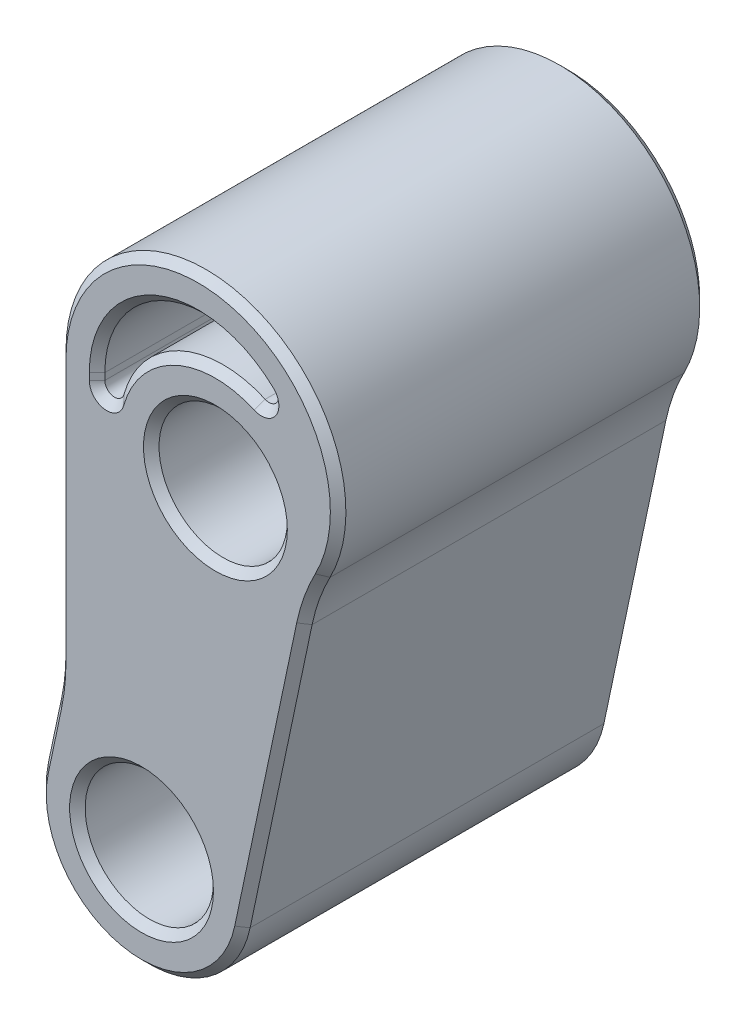
SolidWorks part; units mm, degrees
ref_plane "Front" through (0, 0, 0) normal (0, 0, 1) x (1, 0, 0)
ref_plane "Top" through (0, 0, 0) normal (0, 1, 0) x (1, 0, 0)
ref_plane "Right" through (0, 0, 0) normal (1, 0, 0) x (0, 0, -1)
sketch "Sketch1" plane through (0, 0, 0) normal (0, 0, 1) x (1, 0, 0)
  line L3 (-2.65, 0) -> (-1.65, 0) construction
  line L23 (-0.25, -9) -> (0.75, -9) construction
  line L33 (-2.5929, 0.5474) -> (-4.4929, -8.4526)
  line L34 (0.6929, -9.5474) -> (2.5929, -0.5474)
  circle A0 centre (0, 0) radius 2.65 construction
  circle A3 centre (0, 0) radius 1.65
  circle A12 centre (-1.9, -9) radius 1.65
  circle A13 centre (-1.9, -9) radius 4 construction
  arc A22 (-2.5929, 0.5474) -> (2.5929, -0.5474) centre (0, 0) cw
  arc A28 (-4.4929, -8.4526) -> (0.6929, -9.5474) centre (-1.9, -9) ccw
  dimension "D1" = 3.3
  dimension "D3" = 8
  dimension "D2" = 1
  dimension "D6" = 9
  dimension "D4" = 1.9
extrude "Boss-Extrude1" add sketch "Sketch1" along normal mid plane 9.5 contours A3 region at (-0.95, -4.5, 0)
sketch "Sketch2" plane through (0, 0, 0) normal (0, 0, 1) x (1, 0, 0)
  line L0 (-4.0437, -6.3253) -> (-4.0437, 0.9516)
  line L1 (0, 0) -> (0, 8.0844) construction
  line L2 (0, 0) -> (-0.4437, 0.9516) construction
  line L3 (-0.4437, 0.9516) -> (-1.7961, 3.8518) construction
  line L4 (-1.7961, 3.8518) -> (-1.9652, 4.2143) construction
  line L5 (-2.5929, 0.5474) -> (-4.4929, -8.4526) construction
  line L6 (-2.5929, 0.5474) -> (-4.4929, -8.4526) construction
  arc A0 (-4.0437, 0.9516) -> (2.1622, -1.5322) centre (-0.4437, 0.9516) cw
  circle A1 centre (0, 0) radius 4.25 construction
  arc A4 (2.5929, -0.5474) -> (-2.5929, 0.5474) centre (0, 0) ccw construction
  dimension "D2" = 8.5
  dimension "D4" = 3.6
  dimension "D1" = 0.4
  dimension "D3" = 25
extrude "Spring" add sketch "Sketch2" along normal through all and the other way through all thin thin type one direction wall 1
fillet "Spring Inside Fillets" radius 0.25 2 edges at (-3.0437, -1.5885, 0) (2.0536, 1.6748, 0)
fillet "Spring Outside Fillets" radius 5 2 edges at (-4.0437, -6.3253, 0) (2.4601, -1.1762, 0)
chamfer "Deburs" distance 0.2 angle 45 28 edges at (1.65, 0, -4.75) (-0.25, -9, -4.75) (-1.4639, 3.3431, -4.75) (1.3901, 2.5083, -4.75) (-2.8276, 0.5301, -4.75) (-3.0437, 0.8647, -4.75) (-2.4474, -11.5929, -4.75) (1.4898, -5.7724, -4.75) (-1.1278, 2.398, -4.75) (0.4144, 4.4478, -4.75) (-4.0437, -2.4258, -4.75) (-4.0708, -6.3225, -4.75) (-0.25, -9, 4.75) (1.65, 0, 4.75) (1.3901, 2.5083, 4.75) (-1.4639, 3.3431, 4.75) (-3.0437, 0.8647, 4.75) (-2.8276, 0.5301, 4.75) (0.4144, 4.4478, 4.75) (-1.1278, 2.398, 4.75) (1.4898, -5.7724, 4.75) (-2.4474, -11.5929, 4.75) (-4.0708, -6.3225, 4.75) (-4.0437, -2.4258, 4.75) (-4.3222, -7.6443, -4.75) (-4.3222, -7.6443, 4.75) (2.473, -1.3406, -4.75) (2.473, -1.3406, 4.75)
equation "\"D1@Sketch1\"=\"Hardware Clearance Hole Diameter@Box Assy.Assembly\"+.15mm"
